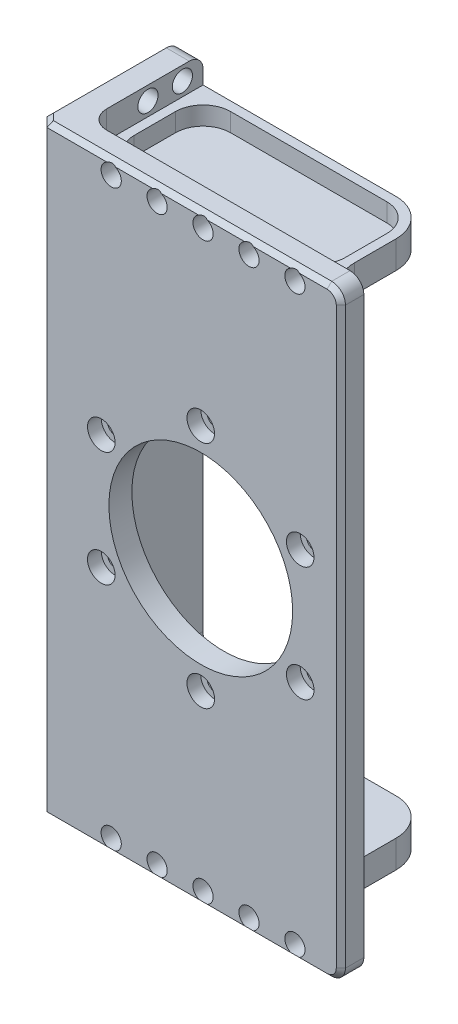
SolidWorks part; units mm, degrees
material "7075-T6 (SN)"
ref_plane "前视基准面" through (0, 0, 0) normal (0, 0, 1) x (1, 0, 0)
ref_plane "上视基准面" through (0, 0, 0) normal (0, 1, 0) x (1, 0, 0)
ref_plane "右视基准面" through (0, 0, 0) normal (1, 0, 0) x (0, 0, -1)
sketch "草图1" plane through (0, 0, 0) normal (0, 0, 1) x (1, 0, 0)
  line L0 (-237.1759, 120) -> (-237.1759, 1) construction
  line L1 (-237.1759, 60.5) -> (-177.1759, 60.5) construction
  line L2 (812.8241, 60.5) -> (-387.1759, 60.5) construction
  line L3 (-165.4601, -5) -> (-232.1759, -5) construction
  line L4 (-237.1759, 126) -> (-177.1759, 126)
  line L5 (-237.1759, 126) -> (-237.1759, -5)
  line L6 (-237.1759, -5) -> (-177.1759, -5)
  line L7 (-177.1759, 126) -> (-177.1759, -5)
extrude "凸台-拉伸1" add sketch "草图1" along normal blind 5
sketch "草图2" plane through (-237.1759, 0, 0) normal (-1, 0, 0) x (0, 0, 1)
  line L0 (-235, 126) -> (-5, 126) construction
  line L1 (5, -5) -> (-25, -5)
  line L2 (5, -5) -> (5, 126)
  line L3 (5, 126) -> (-25, 126)
  line L4 (-25, -5) -> (-25, 126)
extrude "凸台-拉伸2" add sketch "草图2" along normal blind 6
sketch "草图3" plane through (0, 0, 5) normal (0, 0, 1) x (1, 0, 0)
  line L2 (-236.1759, 60.5) -> (-179.1759, 60.5) construction
  circle A2 centre (-207.6759, 60.5) radius 28.5 construction
  circle A3 centre (-207.6759, 60.5) radius 25 construction
  circle A4 centre (-207.6759, 60.5) radius 20
  dimension "D1" = 5
extrude "切除-拉伸1" cut sketch "草图3" against normal blind 10
sketch "草图4" plane through (0, 0, 5) normal (0, 0, 1) x (1, 0, 0)
  line L4 (-177.1759, 126) -> (-243.1759, 126)
  line L5 (-243.1759, 126) -> (-243.1759, -5)
  line L6 (-243.1759, -5) -> (-177.1759, -5)
  line L7 (-177.1759, -5) -> (-177.1759, 126)
  line L8 (-177.1759, 126) -> (-243.1759, 126)
  line L9 (-243.1759, 126) -> (-243.1759, -5)
  line L10 (-243.1759, -5) -> (-177.1759, -5)
  line L11 (-177.1759, -5) -> (-177.1759, 126)
  circle A0 centre (-207.6759, 60.5) radius 20 construction
  circle A1 centre (-207.6759, 60.5) radius 20
  dimension "D1" = 0
chamfer "倒角1" distance 2 angle 45 1 edges at (-243.1759, 60.5, 5)
fillet "圆角1" radius 3 4 edges at (-240.1759, 126, -25) (-177.1759, 126, 2.5) (-177.1759, -5, 2.5) (-240.1759, -5, -25)
sketch "草图5" plane through (0, 0, 5) normal (0, 0, 1) x (1, 0, 0)
  circle A0 centre (-207.6759, 60.5) radius 25 construction
  point P3 (-207.6759, 85.5)
  point P4 (-186.0252, 73)
  point P7 (-186.0252, 48)
  point P8 (-207.6759, 35.5)
  point P9 (-229.3265, 48)
  point P10 (-229.3265, 73)
  point P11 (-207.6759, 60.5)
  dimension "D1" = 6
sketch "草图13" plane through (0, 0, 5) normal (0, 0, 1) x (1, 0, 0)
  circle A0 centre (-207.6759, 85.5) radius 1.6
  circle A1 centre (-229.3265, 73) radius 1.6
  circle A2 centre (-186.0252, 73) radius 1.6
  circle A3 centre (-186.0252, 48) radius 1.6
  circle A4 centre (-207.6759, 35.5) radius 1.6
  circle A5 centre (-229.3265, 48) radius 1.6
extrude "切除-拉伸2" cut sketch "草图13" against normal blind 6
sketch "草图14" plane through (0, 0, 5) normal (0, 0, 1) x (1, 0, 0)
  circle A0 centre (-207.6759, 85.5) radius 3
  circle A1 centre (-186.0252, 73) radius 3
  circle A2 centre (-186.0252, 48) radius 3
  circle A3 centre (-207.6759, 35.5) radius 3
  circle A4 centre (-229.3265, 48) radius 3
  circle A5 centre (-229.3265, 73) radius 3
extrude "切除-拉伸3" cut sketch "草图14" against normal blind 3
chamfer "倒角4" distance 1 angle 45 12 edges at (-242.1759, -5, 4) (-210.6759, -5, 5) (-243.1759, -5, -9.5) (-178.0545, -4.1213, 5) (-243.1759, -4.1213, -24.1213) (-177.1759, 60.5, 5) (-243.1759, 60.5, -25) (-178.0545, 125.1213, 5) (-243.1759, 125.1213, -24.1213) (-210.6759, 126, 5) (-242.1759, 126, 4) (-243.1759, 126, -9.5)
sketch "草图15" plane through (0, 0, 0) normal (0, -1, 0) x (1, 0, 0)
  line L0 (-11.5, -120) -> (-5.5, -120) construction
  line L1 (-11.5, -193) -> (-11.5, -47) construction
  line L2 (-5.5, -108) -> (-5.5, -132) construction
  line L3 (-8.5, -100) -> (-8.5, -140) construction
  line L4 (-8.5, -80) -> (-8.5, -160) construction
  line L5 (-8.5, -60) -> (-8.5, -180) construction
  point P9 (-8.5, -120)
  point P13 (-8.5, -120)
  point P16 (-8.5, -120)
sketch "草图16" plane through (0, 0, 0) normal (0, 0, -1) x (-1, 0, 0)
  line L5 (237.1759, 126) -> (237.1759, 120) construction
  line L6 (237.1759, 123) -> (237.1759, -2) construction
  line L8 (237.1759, 120) -> (187.1759, 120)
  line L9 (237.1759, 120) -> (237.1759, 114)
  line L10 (237.1759, 114) -> (187.1759, 114)
  line L11 (187.1759, 120) -> (187.1759, 114)
extrude "凸台-拉伸4" add sketch "草图16" along normal up to surface (25 mm away) up to face at (-239.6759, 60.5, -25)
ref_plane "基准面1" through (0, 60.5, 0) normal (0, -1, 0) x (-1, 0, 0)
mirror "镜向1" about plane through (0, 60.5, 0) normal (0, -1, 0) of "凸台-拉伸4"
fillet "圆角3" radius 4 2 edges at (-237.1759, -2, 0) (-237.1759, 123, 0)
fillet "圆角4" radius 10 2 edges at (-237.1759, 114, -12.5) (-237.1759, 7, -12.5)
fillet "圆角5" radius 8 4 edges at (-187.1759, 117, 0) (-187.1759, 117, -25) (-187.1759, 4, 0) (-187.1759, 4, -25)
sketch "草图17" plane through (0, 120, 0) normal (0, 1, 0) x (1, 0, 0)
  line L4 (-235.1759, 4) -> (-235.1759, 2)
  line L5 (-235.1759, 2) -> (-233.1759, 2)
  line L8 (-189.1759, 8) -> (-189.1759, 17)
  line L9 (-195.1759, 23) -> (-235.1759, 23)
  line L10 (-235.1759, 23) -> (-235.1759, 4)
  line L11 (-233.1759, 2) -> (-187.1759, 2)
  line L12 (-189.1759, 8) -> (-189.1759, 17)
  line L13 (-195.1759, 23) -> (-235.1759, 23)
  line L14 (-235.1759, 23) -> (-235.1759, 4)
  line L15 (-233.1759, 2) -> (-187.1759, 2)
  arc A6 (-189.1759, 17) -> (-195.1759, 23) centre (-195.1759, 17) ccw
  arc A7 (-235.1759, 4) -> (-233.1759, 2) centre (-233.1759, 4) ccw
  arc A8 (-189.1759, 8) -> (-187.1759, 2) centre (-179.1759, 8) ccw
  arc A9 (-189.1759, 17) -> (-195.1759, 23) centre (-195.1759, 17) ccw
  arc A11 (-189.1759, 8) -> (-187.1759, 2) centre (-179.1759, 8) ccw
  dimension "D1" = 2
extrude "切除-拉伸4" cut sketch "草图17" against normal blind 4
mirror "镜向2" about plane through (0, 60.5, 0) normal (0, -1, 0) of "切除-拉伸4"
fillet "圆角6" radius 6 6 edges at (-187.1759, 118, -2) (-235.1759, 118, -23) (-235.1759, 118, -2) (-235.1759, 3, -23) (-187.1759, 3, -2) (-235.1759, 3, -2)
sketch "草图19" plane through (0, 0, 5) normal (0, 0, 1) x (1, 0, 0)
  line L0 (-243.1759, -5) -> (-237.1759, -5) construction
  line L1 (-243.1759, -5) -> (-177.1759, -5) construction
  line L2 (-237.1759, -5) -> (-177.1759, -5) construction
  line L3 (-207.1759, -5) -> (-207.1759, 1) construction
  line L4 (-217.1759, -2) -> (-197.1759, -2)
  line L5 (-227.1759, -2) -> (-187.1759, -2)
  circle A0 centre (-227.1759, -2) radius 2.2
  circle A1 centre (-217.1759, -2) radius 2.2
  circle A2 centre (-207.1759, -2) radius 2.2
  circle A3 centre (-197.1759, -2) radius 2.2
  circle A4 centre (-187.1759, -2) radius 2.2
  point P13 (-207.1759, -2)
  point P15 (-207.1759, -2)
extrude "切除-拉伸5" cut sketch "草图19" against normal blind 18
mirror "镜向3" about plane through (0, 60.5, 0) normal (0, -1, 0) of "切除-拉伸5"
sketch "草图20" plane through (-243.1759, 0, 0) normal (-1, 0, 0) x (0, 0, 1)
  line L0 (5, -5) -> (-1, -5) construction
  line L1 (5, -5) -> (5, 126) construction
  line L2 (4, -5) -> (2.5858, -5) construction
  line L3 (-1, -5) -> (-25, -5) construction
  line L4 (-5, -5) -> (-235, -5) construction
  line L5 (-13, -5) -> (-13, 1) construction
  line L6 (-20.5, -2) -> (-5.5, -2) construction
  circle A0 centre (-20.5, -2) radius 2.2
  circle A1 centre (-13, -2) radius 2.2
  point P15 (-13, -2)
extrude "切除-拉伸6" cut sketch "草图20" against normal blind 18
mirror "镜向4" about plane through (0, 60.5, 0) normal (0, -1, 0) of "切除-拉伸6"
